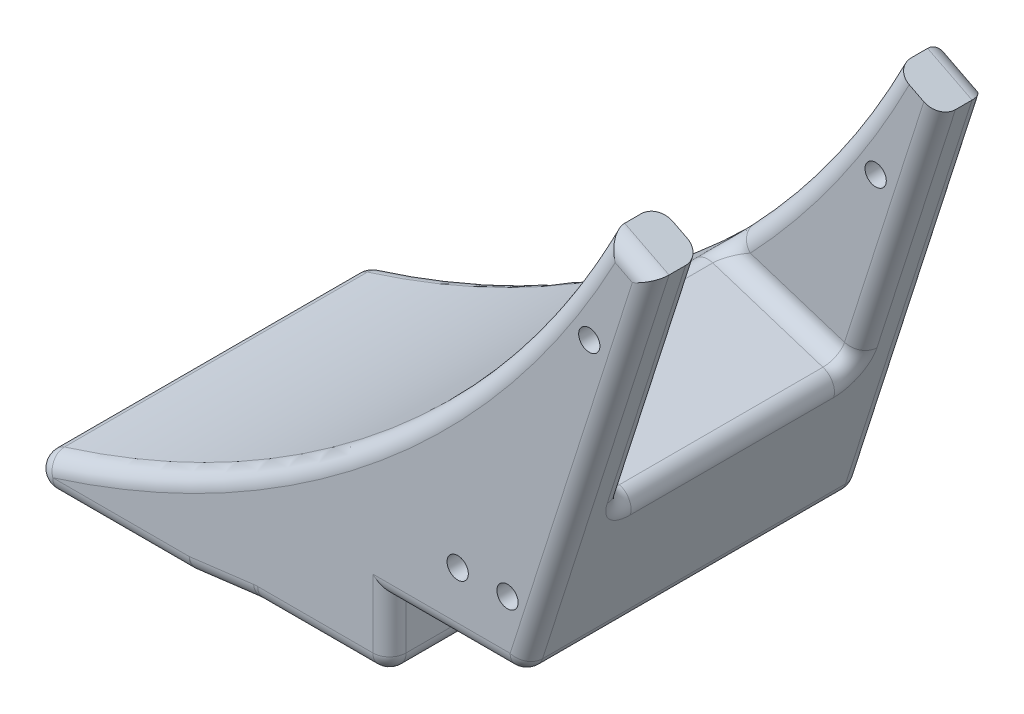
SolidWorks part; units mm, degrees
ref_plane "Front Plane" through (0, 0, 0) normal (0, 0, 1) x (1, 0, 0)
ref_plane "Top Plane" through (0, 0, 0) normal (0, 1, 0) x (1, 0, 0)
ref_plane "Right Plane" through (0, 0, 0) normal (1, 0, 0) x (0, 0, -1)
sketch "Sketch1" plane through (0, 0, 0) normal (0, 0, 1) x (1, 0, 0)
  line L3 (0, 0) -> (19.5546, 0) construction
  line L11 (-25.4, 0) -> (0, 0)
  line L14 (-92.075, -1.5875) -> (-38.1, -1.5875)
  line L15 (-38.1, -1.5875) -> (-25.4, 0)
  line L16 (169.1053, 345.5087) -> (0.5868, 14.2189) construction
  line L18 (0, 13.0653) -> (0, 0)
  line L21 (25.4, 13.0653) -> (0, 13.0653)
  line L22 (41.8052, 95.25) -> (50.295, 90.9315)
  line L23 (50.295, 90.9315) -> (25.4, 13.0653)
  line L25 (25.4, 7.3503) -> (25.4, 3.5403) construction
  arc A2 (-92.075, -1.5875) -> (41.8052, 95.25) centre (-119.5097, 177.3067) ccw
  point P4 (0, 13.0653)
  point P14 (-92.075, -1.5875)
  point P17 (0, 0)
  dimension "D4" = 9.525
  dimension "D3" = 95.25
  dimension "D1" = 92.075
  dimension "D2" = 1.5875
  dimension "D5" = 81.749
  dimension "D6" = 12.7
  dimension "D7" = 25.4
extrude "Boss-Extrude1" add sketch "Sketch1" along normal blind 64.2938
sketch "Sketch5" plane through (19.2547, -6.156, 0) normal (0.9525, -0.3045, 0) x (0, 0, -1)
  line L0 (-64.2938, 103.4568) -> (0, 103.4568) construction
  line L1 (-54.7687, 103.4568) -> (-9.525, 103.4568)
  line L2 (-54.7687, 103.4568) -> (-54.7687, 49.4818)
  line L3 (-54.7687, 49.4818) -> (-9.525, 49.4818)
  line L4 (-9.525, 103.4568) -> (-9.525, 49.4818)
  line L5 (-64.2938, 20.1798) -> (-64.2938, 101.9288) construction
  line L6 (0, 20.1798) -> (0, 101.9288) construction
  dimension "D1" = 9.525
  dimension "D2" = 9.525
  dimension "D3" = 53.975
extrude "Cut-Extrude3" cut sketch "Sketch5" against normal up to surface (9.4016 mm away) up to face at (-19.287, 38.7464, 32.1469)
fillet "Fillet2" radius 3.175 29 edges at (26.919, 70.9373, 9.525) (42.3092, 65.9535, 9.525) (42.3092, 65.9535, 54.7687) (26.919, 70.9373, 54.7687) (-38.1, -1.5875, 32.1469) (-25.4, 0, 32.1469) (21.3615, 45.1197, 9.525) (34.3233, 40.9756, 32.1469) (21.3615, 45.1197, 54.7687) (8.3997, 49.2638, 32.1469) (12.7, 13.0653, 0) (37.8475, 51.9984, 0) (46.0501, 93.0907, 0) (-13.4391, 30.6615, 0) (-65.0875, -1.5875, 0) (-31.75, -0.7938, 0) (-12.7, 0, 0) (0, 6.5326, 0) (-12.7, 0, 64.2938) (-31.75, -0.7938, 64.2938) (-65.0875, -1.5875, 64.2938) (-13.4391, 30.6615, 64.2938) (46.0501, 93.0907, 64.2938) (37.8475, 51.9984, 64.2938) (12.7, 13.0653, 64.2938) (0, 6.5326, 64.2938) (25.4, 13.0653, 32.1469) (0, 0, 32.1469) (-92.075, -1.5875, 32.1469)
sketch "Sketch6" plane through (0, 0, 64.2938) normal (0, 0, 1) x (1, 0, 0)
  line L0 (41.8052, 95.25) -> (50.295, 90.9315) construction
  line L2 (38.2114, 75.7051) -> (44.7577, 73.6122) construction
  line L3 (50.295, 90.9315) -> (26.106, 15.2734) construction
  line L4 (38.2114, 75.7051) -> (31.6652, 77.7981) construction
  line L5 (22.5715, 25.4) -> (29.3436, 25.4) construction
  line L6 (23.0818, 13.0653) -> (0, 13.0653) construction
  line L7 (13.0465, 25.4) -> (6.2743, 25.4) construction
  line L8 (169.1053, 345.5087) -> (0.5868, 14.2189) construction
  circle A0 centre (13.0465, 25.4) radius 2.032
  circle A1 centre (22.5715, 25.4) radius 2.032
  circle A2 centre (38.2114, 75.7051) radius 2.032
  arc A3 (-65.3428, 4.617) -> (41.8052, 95.25) centre (-119.5097, 177.3067) ccw construction
  dimension "D1" = 4.064
  dimension "D2" = 19.05
  dimension "D3" = 9.525
  dimension "D4" = 25.4
extrude "Cut-Extrude4" cut sketch "Sketch6" against normal blind 9.525
ref_plane "Plane1" through (0, 0, 32.1469) normal (0, 0, 1) x (1, 0, 0)
mirror "Mirror1" about plane through (0, 0, 32.1469) normal (0, 0, 1) of "Cut-Extrude4"
sketch "Sketch7" plane through (0, 13.0653, 0) normal (0, -1, 0) x (1, 0, 0)
  line L0 (0, 61.1187) -> (0, 3.175) construction
  line L1 (6.35, 13.0969) -> (6.35, 0) construction
  line L2 (23.0818, 0) -> (-3.175, 0) construction
  line L3 (6.35, 51.1969) -> (6.35, 64.2938) construction
  line L4 (-3.175, 64.2938) -> (23.0818, 64.2938) construction
  circle A0 centre (6.35, 13.0969) radius 1.905
  circle A1 centre (6.35, 51.1969) radius 1.905
  circle A2 centre (19.05, 51.1969) radius 1.905
  circle A3 centre (19.05, 13.0969) radius 1.905
  dimension "D2" = 3.81
  dimension "D1" = 6.35
  dimension "D3" = 38.1
  dimension "D4" = 12.7
extrude "Cut-Extrude5" cut sketch "Sketch7" against normal blind 12.7
